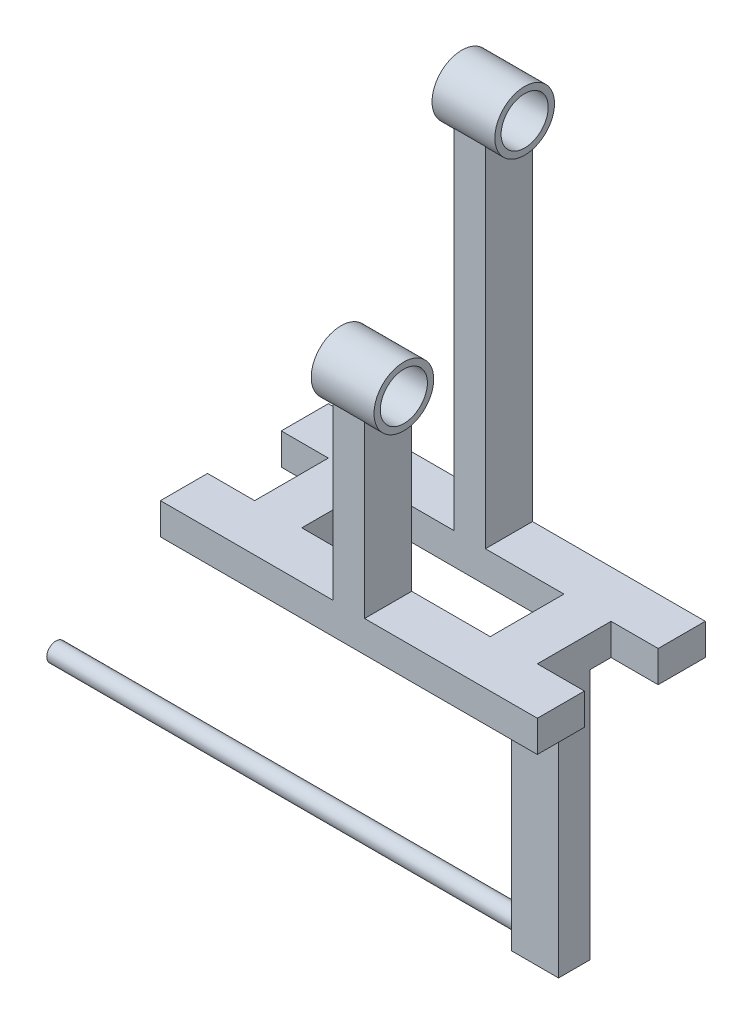
SolidWorks part; units mm, degrees
ref_plane "Front Plane" through (0, 0, 0) normal (0, 0, 1) x (1, 0, 0)
ref_plane "Top Plane" through (0, 0, 0) normal (0, 1, 0) x (1, 0, 0)
ref_plane "Right Plane" through (0, 0, 0) normal (1, 0, 0) x (0, 0, -1)
sketch "Sketch2" plane through (0, 0, 0) normal (0, 1, 0) x (1, 0, 0)
  line L33 (60, -15) -> (-60, -15)
  line L34 (-60, -15) -> (-60, 0)
  line L46 (-60, 0) -> (-45, 0)
  line L47 (-45, 0) -> (-45, 23.4666)
  line L48 (-45, 23.4666) -> (-60, 23.4666)
  line L49 (-60, 23.4666) -> (-60, 38.4666)
  line L50 (-60, 38.4666) -> (60, 38.4666)
  line L51 (60, 38.4666) -> (60, 23.4666)
  line L52 (60, 23.4666) -> (45, 23.4666)
  line L53 (45, 23.4666) -> (45, 0)
  line L54 (45, 0) -> (60, 0)
  line L55 (60, 0) -> (60, -15)
  line L57 (-30, 0) -> (30, 0)
  line L58 (-30, 0) -> (-30, 23.4666)
  line L59 (-30, 23.4666) -> (30, 23.4666)
  line L60 (30, 0) -> (30, 23.4666)
  point P21 (0, 0)
  dimension "D1" = 120
  dimension "D2" = 53.4666
  dimension "D3" = 15
  dimension "D4" = 60
  dimension "D5" = 15
  dimension "D6" = 15
extrude "Boss-Extrude2" add sketch "Sketch2" along normal blind 10
sketch "Sketch3" plane through (0, 10, 0) normal (0, 1, 0) x (1, 0, 0)
  line L0 (-30, 0) -> (30, 0) construction
  line L1 (-5, 0) -> (5, 0)
  line L2 (-5, 0) -> (-5, -15)
  line L3 (-5, -15) -> (5, -15)
  line L4 (5, 0) -> (5, -15)
  line L5 (-60, -15) -> (60, -15) construction
  line L6 (60, 38.4666) -> (-60, 38.4666) construction
  line L7 (-5, 38.4666) -> (5, 38.4666)
  line L8 (-5, 38.4666) -> (-5, 23.4666)
  line L9 (-5, 23.4666) -> (5, 23.4666)
  line L10 (5, 38.4666) -> (5, 23.4666)
  line L11 (30, 23.4666) -> (-30, 23.4666) construction
  dimension "D1" = 5
  dimension "D2" = 10
extrude "Boss-Extrude3" add sketch "Sketch3" along normal blind 60
sketch "Sketch4" plane through (0, 70, 0) normal (0, 1, 0) x (1, 0, 0)
  line L4 (-5, 38.4666) -> (-5, 23.4666)
  line L5 (-5, 23.4666) -> (5, 23.4666)
  line L6 (5, 23.4666) -> (5, 38.4666)
  line L7 (5, 38.4666) -> (-5, 38.4666)
  line L8 (-5, 38.4666) -> (-5, 23.4666)
  line L9 (-5, 23.4666) -> (5, 23.4666)
  line L10 (5, 23.4666) -> (5, 38.4666)
  line L11 (5, 38.4666) -> (-5, 38.4666)
  dimension "D1" = 0
extrude "Boss-Extrude4" add sketch "Sketch4" along normal blind 56.7503
sketch "Sketch6" plane through (0, 0, 0) normal (1, 0, 0) x (0, 0, -1)
  line L0 (-15, 70) -> (0, 70) construction
  line L1 (23.4666, 126.7503) -> (38.4666, 126.7503) construction
  line L2 (0, 70) -> (0, 10) construction
  line L3 (38.4666, 126.7503) -> (38.4666, 10) construction
  circle A0 centre (-7.5, 70) radius 7.5
  circle A1 centre (30.9666, 126.7503) radius 7.5
  dimension "D1" = 15
  dimension "D2" = 7.5
  dimension "D3" = 7.5
extrude "Extrude-Thin1" add sketch "Sketch6" along normal mid plane 20 thin thin type one direction wall 2
sketch "Sketch7" plane through (5, 0, 0) normal (1, 0, 0) x (0, 0, -1)
  line L1 (0, 70) -> (-15, 70)
  line L2 (0, 70) -> (-15, 70)
  line L3 (38.4666, 126.7503) -> (23.4666, 126.7503)
  line L4 (38.4666, 126.7503) -> (23.4666, 126.7503)
  arc A1 (-15, 70) -> (0, 70) centre (-7.5, 70) ccw
  arc A2 (-15, 70) -> (0, 70) centre (-7.5, 70) ccw
  arc A3 (23.4666, 126.7503) -> (38.4666, 126.7503) centre (30.9666, 126.7503) ccw
  arc A4 (23.4666, 126.7503) -> (38.4666, 126.7503) centre (30.9666, 126.7503) ccw
  dimension "D1" = 0
  dimension "D2" = 0
extrude "Cut-Extrude1" cut sketch "Sketch7" against normal through all both and the other way through all
sketch "Sketch8" plane through (0, 0, 0) normal (0, -1, 0) x (1, 0, 0)
  line L0 (30, 0) -> (30, -23.4666) construction
  line L1 (30, -16.75) -> (45, -16.75)
  line L2 (30, -16.75) -> (30, -6.75)
  line L3 (30, -6.75) -> (45, -6.75)
  line L4 (45, -16.75) -> (45, -6.75)
  line L5 (45, 0) -> (45, -23.4666) construction
  line L6 (-60, 15) -> (60, 15) construction
  dimension "D1" = 10
  dimension "D2" = 21.75
extrude "Boss-Extrude5" add sketch "Sketch8" along normal blind 80
sketch "Sketch9" plane through (30, 0, 0) normal (-1, 0, 0) x (0, 0, 1)
  line L0 (-6.75, -80) -> (-6.75, 0) construction
  line L1 (-6.75, -80) -> (-16.75, -80) construction
  circle A0 centre (-11.75, -75) radius 2.95
  dimension "D1" = 5.9
  dimension "D2" = 5
  dimension "D3" = 5
extrude "Boss-Extrude6" add sketch "Sketch9" along normal blind 150
